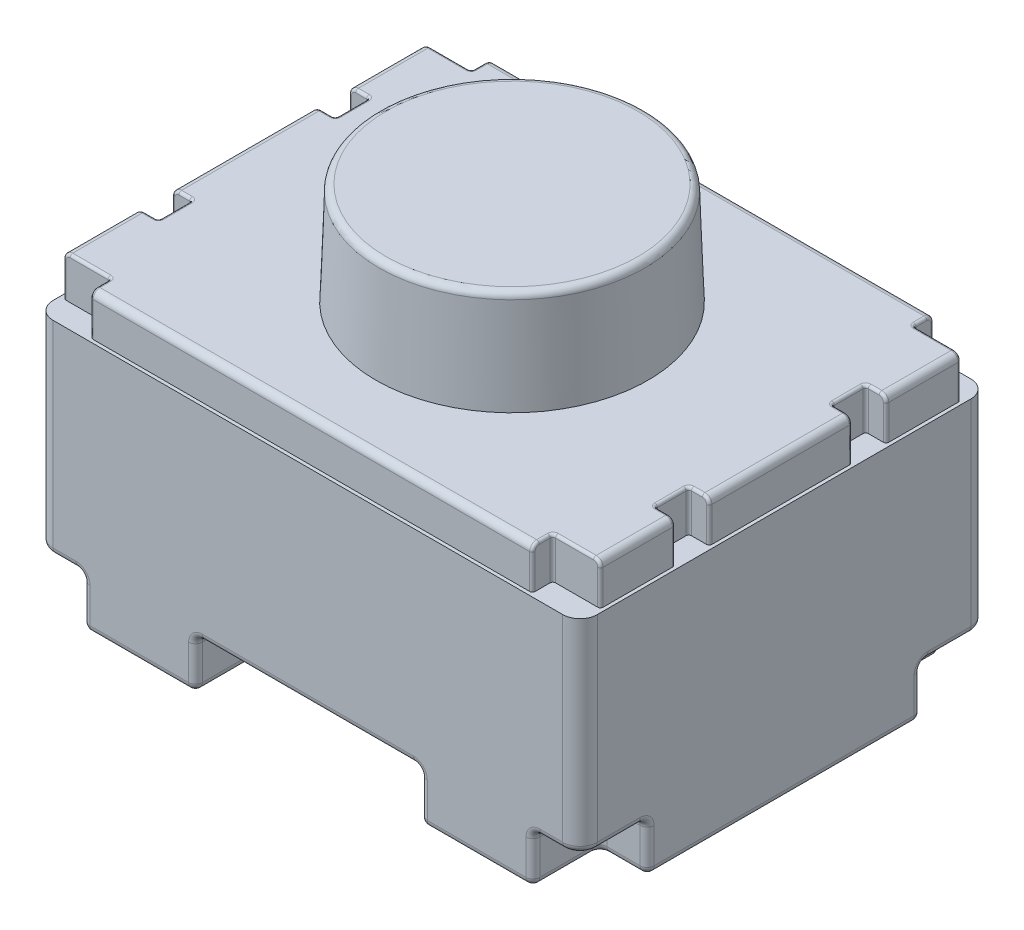
SolidWorks part; units mm, degrees
ref_plane "Front Plane" through (0, 0, 0) normal (0, 0, 1) x (1, 0, 0)
ref_plane "Top Plane" through (0, 0, 0) normal (0, 1, 0) x (1, 0, 0)
ref_plane "Right Plane" through (0, 0, 0) normal (1, 0, 0) x (0, 0, -1)
sketch "Sketch1" plane through (0, 0, 0) normal (0, 1, 0) x (1, 0, 0)
  line L1 (-2, -1.5) -> (2, -1.5)
  line L2 (-2, -1.5) -> (-2, 1.5)
  line L3 (-2, 1.5) -> (2, 1.5)
  line L4 (2, -1.5) -> (2, 1.5)
  line L5 (-2, -1.5) -> (2, 1.5) construction
  line L6 (-2, 1.5) -> (2, -1.5) construction
  point P0 (0, 0)
  dimension "D1" = 4
  dimension "D2" = 3
extrude "Boss-Extrude1" add sketch "Sketch1" along normal blind 1.5 from offset 0.5588
fillet "Fillet1" radius 0.127 4 edges at (-2, 1.3088, 1.5) (-2, 1.3088, -1.5) (2, 1.3088, -1.5) (2, 1.3088, 1.5)
sketch "Sketch2" plane through (0, 2.0588, 0) normal (0, -1, 0) x (-1, 0, 0)
  line L8 (1.9746, -1.373) -> (1.9746, 1.373)
  line L9 (-1.873, -1.4746) -> (1.873, -1.4746)
  line L10 (-1.9746, 1.373) -> (-1.9746, -1.373)
  line L11 (1.873, 1.4746) -> (-1.873, 1.4746)
  line L12 (1.9746, -1.373) -> (1.9746, 1.373)
  line L13 (-1.873, -1.4746) -> (1.873, -1.4746)
  line L14 (-1.9746, 1.373) -> (-1.9746, -1.373)
  line L15 (1.873, 1.4746) -> (-1.873, 1.4746)
  arc A8 (1.873, -1.4746) -> (1.9746, -1.373) centre (1.873, -1.373) ccw
  arc A9 (-1.9746, -1.373) -> (-1.873, -1.4746) centre (-1.873, -1.373) ccw
  arc A10 (-1.873, 1.4746) -> (-1.9746, 1.373) centre (-1.873, 1.373) ccw
  arc A11 (1.9746, 1.373) -> (1.873, 1.4746) centre (1.873, 1.373) ccw
  arc A12 (1.873, -1.4746) -> (1.9746, -1.373) centre (1.873, -1.373) ccw
  arc A13 (-1.9746, -1.373) -> (-1.873, -1.4746) centre (-1.873, -1.373) ccw
  arc A14 (-1.873, 1.4746) -> (-1.9746, 1.373) centre (-1.873, 1.373) ccw
  arc A15 (1.9746, 1.373) -> (1.873, 1.4746) centre (1.873, 1.373) ccw
  dimension "D1" = 0.0254
extrude "Boss-Extrude2" add sketch "Sketch2" against normal blind 0.3048
sketch "Sketch3" plane through (0, 0, 0) normal (0, 1, 0) x (1, 0, 0)
  line L0 (-1.6532, -1.5) -> (-1.6532, -1.0069)
  line L1 (-1.873, -1.5) -> (1.873, -1.5) construction
  line L2 (-1.6532, -1.0069) -> (-2, -1.0069)
  line L3 (-2, 1.373) -> (-2, -1.373) construction
  line L4 (-1.5828, -0.4738) -> (-0.8264, -0.4738)
  line L5 (-0.8264, -0.4738) -> (-0.8264, -1.5)
  line L6 (-1.5828, -0.4738) -> (-1.5828, 0.4738)
  line L7 (-1.6532, -1.5) -> (-0.8264, -1.5)
  line L8 (-2, -1.0069) -> (-2, 1.0069)
  line L9 (-1.5828, 0) -> (-2, 0) construction
  line L10 (-1.6532, 1.5) -> (-0.8264, 1.5)
  line L11 (-0.8264, 0.4738) -> (-0.8264, 1.5)
  line L12 (-1.5828, 0.4738) -> (-0.8264, 0.4738)
  line L13 (-1.6532, 1.0069) -> (-2, 1.0069)
  line L14 (-1.6532, 1.5) -> (-1.6532, 1.0069)
  line L15 (0, -1.5) -> (0, 1.5) construction
  line L16 (1.873, 1.5) -> (-1.873, 1.5) construction
  line L17 (1.5828, 0) -> (2, 0) construction
  line L18 (1.6532, 1.5) -> (1.6532, 1.0069)
  line L19 (1.6532, 1.0069) -> (2, 1.0069)
  line L20 (1.5828, 0.4738) -> (0.8264, 0.4738)
  line L21 (0.8264, 0.4738) -> (0.8264, 1.5)
  line L22 (1.6532, 1.5) -> (0.8264, 1.5)
  line L23 (2, -1.0069) -> (2, 1.0069)
  line L24 (1.6532, -1.5) -> (0.8264, -1.5)
  line L25 (1.5828, -0.4738) -> (1.5828, 0.4738)
  line L26 (0.8264, -0.4738) -> (0.8264, -1.5)
  line L27 (1.5828, -0.4738) -> (0.8264, -0.4738)
  line L28 (1.6532, -1.0069) -> (2, -1.0069)
  line L29 (1.6532, -1.5) -> (1.6532, -1.0069)
  dimension "D1" = 3
  dimension "D2" = 4
extrude "Boss-Extrude3" add sketch "Sketch3" along normal up to next from offset 0.2
sketch "Sketch5" plane through (0, 2.3636, 0) normal (0, 1, 0) x (1, 0, 0)
  circle A0 centre (0, 0) radius 1
  dimension "D1" = 2
extrude "Boss-Extrude5" add sketch "Sketch5" along normal blind 0.75 draft 2
fillet "Fillet3" radius 0.0508 88 edges at (1.9628, 0.5588, 1.4628) (1.9628, 0.5588, -1.4628) (-1.9628, 0.5588, -1.4628) (-1.9628, 0.5588, 1.4628) (2, 0.5588, 1.19) (2, 0.5588, -1.19) (0.8264, 0.3794, 1.5) (0.8264, 0.3794, -1.5) (1.9448, 2.3636, -1.4448) (0, 2.3636, -1.4746) (-1.9448, 2.3636, -1.4448) (-1.9746, 2.3636, 0) (-1.9448, 2.3636, 1.4448) (0, 2.3636, 1.4746) (1.9448, 2.3636, 1.4448) (1.5828, 0.3794, 0.4738) (0.8264, 0.3794, 0.4738) (0.8264, 0.3794, -0.4738) (1.5828, 0.3794, -0.4738) (-0.8264, 0.3794, 0.4738) (-1.5828, 0.3794, 0.4738) (-1.5828, 0.3794, -0.4738) (-0.8264, 0.3794, -0.4738) (1.8266, 0.5588, 1.0069) (2, 0.3794, 1.0069) (1.6532, 0.3794, 1.5) (1.6532, 0.5588, 1.2535) (1.6532, 0.3794, 1.0069) (2, 0.3794, -1.0069) (1.8266, 0.5588, -1.0069) (1.6532, 0.3794, -1.0069) (1.6532, 0.5588, -1.2535) (1.6532, 0.3794, -1.5) (-1.6532, 0.3794, -1.0069) (-1.6532, 0.3794, 1.0069) (-1.2046, 0.5588, -0.4738) (-1.5828, 0.5588, 0) (-1.2046, 0.5588, 0.4738) (0.8264, 0.5588, 0.9869) (1.2046, 0.5588, 0.4738) (1.5828, 0.5588, 0) (1.2046, 0.5588, -0.4738) (0.8264, 0.5588, -0.9869) (-0.8264, 0.2, 0.9869) (-1.2046, 0.2, 0.4738) (-1.5828, 0.2, 0) (-1.2046, 0.2, -0.4738) (-0.8264, 0.2, -0.9869) (-1.2398, 0.2, -1.5) (-1.6532, 0.2, -1.2535) (-1.8266, 0.2, -1.0069) (-2, 0.2, 0) (-1.8266, 0.2, 1.0069) (-1.6532, 0.2, 1.2535) (-1.2398, 0.2, 1.5) (0.8264, 0.2, -0.9869) (1.2046, 0.2, -0.4738) (1.5828, 0.2, 0) (1.2046, 0.2, 0.4738) (0.8264, 0.2, 0.9869) (1.2398, 0.2, 1.5) (1.6532, 0.2, 1.2535) (1.8266, 0.2, 1.0069) (2, 0.2, 0) (1.8266, 0.2, -1.0069) (1.6532, 0.2, -1.2535) (1.2398, 0.2, -1.5) (1.9746, 2.3636, 0)
sketch "Sketch6" plane through (0, 2.3636, 0) normal (0, 1, 0) x (1, 0, 0)
  line L0 (-1.9746, -1.373) -> (-1.9746, 1.373) construction
  line L1 (-1.9746, 0.775) -> (-1.8246, 0.775)
  line L2 (-1.9746, 0.775) -> (-1.9746, 0.525)
  line L3 (-1.9746, 0.525) -> (-1.8246, 0.525)
  line L4 (-1.8246, 0.775) -> (-1.8246, 0.525)
  line L5 (-1.9746, 0.775) -> (-1.8246, 0.525) construction
  line L6 (-1.9746, 0.525) -> (-1.8246, 0.775) construction
  line L7 (0, 0) -> (0, 2.2745) construction
  line L8 (-1.6246, 1.3246) -> (-1.9746, 1.3246)
  line L9 (-1.6246, 1.3246) -> (-1.6246, 1.4746)
  line L10 (-1.6246, 1.4746) -> (-1.873, 1.4746)
  line L11 (-1.9746, 1.3246) -> (-1.9746, 1.373)
  line L12 (-1.6246, 1.3246) -> (-1.8858, 1.4738) construction
  line L13 (-1.6246, 1.4746) -> (-1.9746, 1.3246) construction
  line L14 (0, 0) -> (-4.562, 0) construction
  line L15 (1.6246, 1.4746) -> (1.9746, 1.3246) construction
  line L16 (1.6246, 1.3246) -> (1.8858, 1.4738) construction
  line L17 (1.9746, 0.525) -> (1.8246, 0.775) construction
  line L18 (1.9746, 0.775) -> (1.8246, 0.525) construction
  line L19 (1.9746, 1.3246) -> (1.9746, 1.373)
  line L20 (1.6246, 1.4746) -> (1.873, 1.4746)
  line L21 (1.6246, 1.3246) -> (1.6246, 1.4746)
  line L22 (1.6246, 1.3246) -> (1.9746, 1.3246)
  line L23 (1.8246, 0.775) -> (1.8246, 0.525)
  line L24 (1.9746, 0.525) -> (1.8246, 0.525)
  line L25 (1.9746, 0.775) -> (1.9746, 0.525)
  line L26 (1.9746, 0.775) -> (1.8246, 0.775)
  line L27 (1.9746, -0.775) -> (1.8246, -0.525) construction
  line L28 (1.9746, -0.525) -> (1.8246, -0.775) construction
  line L29 (1.6246, -1.3246) -> (1.8858, -1.4738) construction
  line L30 (1.6246, -1.4746) -> (1.9746, -1.3246) construction
  line L31 (-1.6246, -1.4746) -> (-1.9746, -1.3246) construction
  line L32 (-1.6246, -1.3246) -> (-1.8858, -1.4738) construction
  line L33 (-1.9746, -0.525) -> (-1.8246, -0.775) construction
  line L34 (-1.9746, -0.775) -> (-1.8246, -0.525) construction
  line L35 (1.9746, -0.775) -> (1.8246, -0.775)
  line L36 (1.9746, -0.775) -> (1.9746, -0.525)
  line L37 (1.9746, -0.525) -> (1.8246, -0.525)
  line L38 (1.8246, -0.775) -> (1.8246, -0.525)
  line L39 (1.6246, -1.3246) -> (1.9746, -1.3246)
  line L40 (1.6246, -1.3246) -> (1.6246, -1.4746)
  line L41 (1.6246, -1.4746) -> (1.873, -1.4746)
  line L42 (1.9746, -1.3246) -> (1.9746, -1.373)
  line L43 (-1.9746, -1.3246) -> (-1.9746, -1.373)
  line L44 (-1.6246, -1.4746) -> (-1.873, -1.4746)
  line L45 (-1.6246, -1.3246) -> (-1.6246, -1.4746)
  line L46 (-1.6246, -1.3246) -> (-1.9746, -1.3246)
  line L47 (-1.8246, -0.775) -> (-1.8246, -0.525)
  line L48 (-1.9746, -0.525) -> (-1.8246, -0.525)
  line L49 (-1.9746, -0.775) -> (-1.9746, -0.525)
  line L50 (-1.9746, -0.775) -> (-1.8246, -0.775)
  arc A0 (-1.873, 1.4746) -> (-1.9746, 1.373) centre (-1.873, 1.373) ccw construction
  arc A1 (-1.873, 1.4746) -> (-1.9746, 1.373) centre (-1.873, 1.373) ccw
  arc A2 (1.873, 1.4746) -> (1.9746, 1.373) centre (1.873, 1.373) cw
  arc A3 (1.873, -1.4746) -> (1.9746, -1.373) centre (1.873, -1.373) ccw
  arc A4 (-1.873, -1.4746) -> (-1.9746, -1.373) centre (-1.873, -1.373) cw
  point P4 (-1.8996, 0.65)
  point P14 (-1.7747, 1.4103)
  point P30 (1.7747, 1.4103)
  point P31 (1.8996, 0.65)
  point P54 (1.8996, -0.65)
  point P55 (1.7747, -1.4103)
  point P56 (-1.7747, -1.4103)
  point P57 (-1.8996, -0.65)
  dimension "D1" = 0.65
  dimension "D2" = 0.25
  dimension "D3" = 0.15
  dimension "D4" = 0.15
  dimension "D5" = 0.35
extrude "Cut-Extrude1" cut sketch "Sketch6" against normal up to surface (0.3048 mm away) up to face at (0, 2.0588, 0)
fillet "Fillet4" radius 0.02 62 edges at (-1.6246, 2.2112, 1.3246) (-1.6246, 2.1858, 1.4746) (-1.6246, 2.3487, 1.4597) (-1.6246, 2.3636, 1.3742) (-1.7742, 2.3636, 1.3246) (-1.9597, 2.3487, 1.3246) (-1.9746, 2.1858, 1.3246) (-1.9746, 2.1858, 0.525) (-1.9597, 2.3487, 0.525) (-1.8742, 2.3636, 0.525) (-1.8246, 2.2112, 0.525) (-1.8246, 2.3636, 0.65) (-1.8246, 2.2112, 0.775) (-1.8742, 2.3636, 0.775) (-1.9597, 2.3487, 0.775) (-1.9746, 2.1858, 0.775) (-1.9746, 2.1858, -0.525) (-1.9597, 2.3487, -0.525) (-1.8742, 2.3636, -0.525) (-1.8246, 2.2112, -0.525) (-1.8246, 2.3636, -0.65) (-1.8246, 2.2112, -0.775) (-1.8742, 2.3636, -0.775) (-1.9597, 2.3487, -0.775) (-1.9746, 2.1858, -0.775) (-1.9746, 2.1858, -1.3246) (-1.9597, 2.3487, -1.3246) (-1.7742, 2.3636, -1.3246) (-1.6246, 2.2112, -1.3246) (-1.6246, 2.3636, -1.3742) (-1.6246, 2.3487, -1.4597) (-1.6246, 2.1858, -1.4746) (1.6246, 2.1858, -1.4746) (1.6246, 2.3487, -1.4597) (1.6246, 2.3636, -1.3742) (1.9746, 2.1858, -1.3246) (1.9597, 2.3487, -1.3246) (1.7742, 2.3636, -1.3246) (1.6246, 2.2112, -1.3246) (1.8246, 2.2112, -0.775) (1.9746, 2.1858, -0.775) (1.9597, 2.3487, -0.775) (1.8742, 2.3636, -0.775) (1.8246, 2.3636, -0.65) (1.9746, 2.1858, -0.525) (1.8742, 2.3636, -0.525) (1.9597, 2.3487, -0.525) (1.8246, 2.2112, -0.525) (1.9746, 2.1858, 0.525) (1.8742, 2.3636, 0.525) (1.9597, 2.3487, 0.525) (1.8246, 2.2112, 0.525) (1.8246, 2.3636, 0.65) (1.9746, 2.1858, 1.3246) (1.6246, 2.1858, 1.4746) (1.9597, 2.3487, 0.775) (1.8742, 2.3636, 0.775) (1.8246, 2.2112, 0.775) (1.9746, 2.1858, 0.775) (1.6246, 2.2112, 1.3246) (1.6246, 2.3636, 1.3742) (1.7742, 2.3636, 1.3246) tangent propagation no
fillet "Fillet5" radius 0.05 1 edges at (0, 3.1136, 0.9738)
